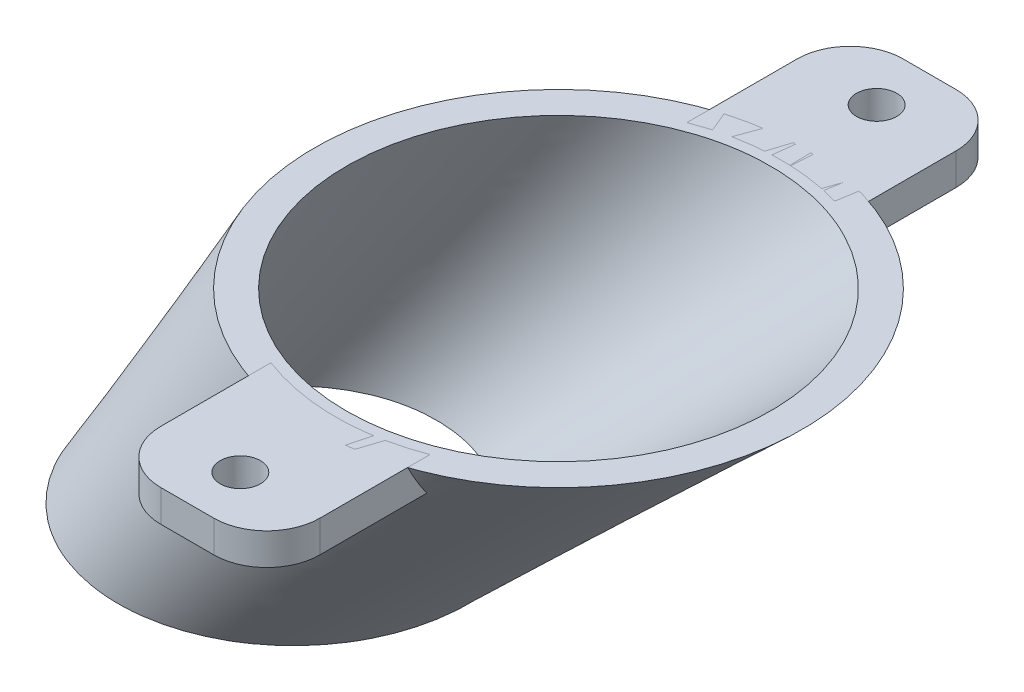
SolidWorks part; units mm, degrees
ref_plane "Front Plane" through (0, 0, 0) normal (0, 0, 1) x (1, 0, 0)
ref_plane "Top Plane" through (0, 0, 0) normal (0, 1, 0) x (1, 0, 0)
ref_plane "Right Plane" through (0, 0, 0) normal (1, 0, 0) x (0, 0, -1)
sketch "Sketch1" plane through (0, 0, 0) normal (0, 1, 0) x (1, 0, 0)
  line L0 (0, 0) -> (-47.9811, 0) construction
  circle A0 centre (0, 0) radius 23
  dimension "D1" = 46
ref_plane "Plane1" through (0, -30, 0) normal (0, -1, 0) x (-1, 0, 0)
sketch "Sketch9" plane through (0, -30, 0) normal (0, -1, 0) x (-1, 0, 0)
  circle A0 centre (25, 0) radius 16.5
  dimension "D1" = 33
  dimension "D2" = 25
loft "Loft1" add profiles "Sketch9", "Sketch1" connector at (-20.6661, -30, -15.9207) connector at (1.0526, 0, -22.9759)
sketch "Sketch13" plane through (0, 0, 0) normal (0, 1, 0) x (1, 0, 0)
  circle A0 centre (0, 0) radius 20
  dimension "D1" = 40
sketch "Sketch14" plane through (0, -30, 0) normal (0, -1, 0) x (1, 0, 0)
  circle A0 centre (-25, 0) radius 13.5
  dimension "D1" = 27
loft "Cut-Loft1" cut profiles "Sketch13", "Sketch14" connector at (-1.7195, 0, 19.9259) connector at (-25.3909, -30, 13.4943)
sketch "Sketch16" plane through (0, 0, 0) normal (0, 1, 0) x (1, 0, 0)
  line L0 (-16.5091, 0) -> (16.5091, 0) construction
  line L1 (-2.5, 35) -> (2.5, 35)
  line L2 (-7.5, 30) -> (-7.5, 19.615)
  line L4 (7.5, 30) -> (7.5, 19.615)
  line L5 (-7.5, -30) -> (-7.5, -19.615)
  line L6 (7.5, -30) -> (7.5, -19.615)
  line L7 (-2.5, -35) -> (2.5, -35)
  circle A0 centre (0, 0) radius 23 construction
  arc A1 (7.5, 19.615) -> (-7.5, 19.615) centre (0, 0) ccw
  arc A2 (2.5, 35) -> (7.5, 30) centre (2.5, 30) cw
  arc A3 (-2.5, 35) -> (-7.5, 30) centre (-2.5, 30) ccw
  arc A4 (7.5, -19.615) -> (-7.5, -19.615) centre (0, 0) cw
  arc A5 (2.5, -35) -> (7.5, -30) centre (2.5, -30) ccw
  arc A6 (-2.5, -35) -> (-7.5, -30) centre (-2.5, -30) cw
  point P0 (0, 23)
  point P8 (0, 21)
  dimension "D2" = 42
  dimension "D4" = 5
  dimension "D1" = 14
  dimension "D3" = 15
extrude "Boss-Extrude1" add sketch "Sketch16" against normal blind 3 separate body
hole_wizard "#10-24 Tapped Hole1" positions "Sketch17" profile "Sketch18" tap size "#10-24" standard "ANSI Inch" end condition through all
sketch "Sketch17" plane through (0, 0, 0) normal (0, 1, 0) x (1, 0, 0)
  line L0 (-2.5, -35) -> (2.5, -35) construction
  line L1 (2.5, 35) -> (-2.5, 35) construction
  point P0 (0, 30)
  point P2 (0, -30)
  dimension "D1" = 5
  dimension "D2" = 5
sketch "Sketch18" plane through (0, 0, -30) normal (1, 0, 0) x (0, 0, 1)
  line L0 (0, 0) -> (0, 30.0083)
  line L1 (0, 30.0083) -> (1.8986, 30.0083)
  line L2 (1.8986, 30.0083) -> (1.8986, 0)
  line L5 (1.8986, 0) -> (0, 0)
  line L11 (0, -6.35) -> (0, 107.95) construction
  dimension "Thru Tap Drill Dia." = 3.7973
  dimension "Thru Tap Drill Depth" = 30.0083
cosmetic thread "Hole Thread1" parameters "D2"=4.826
cosmetic thread "Hole Thread2" parameters "D2"=4.826
